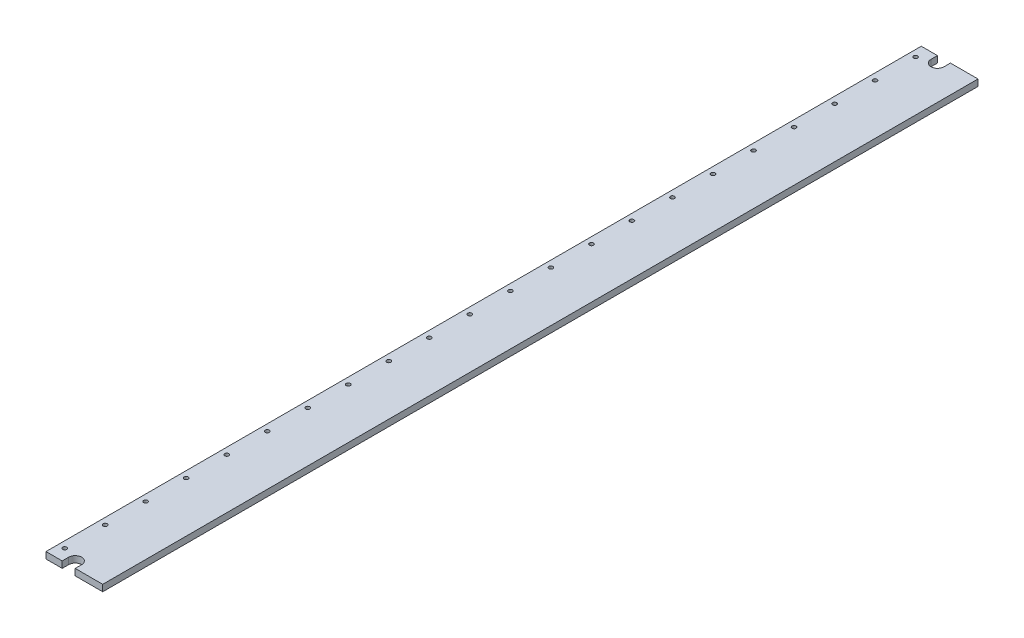
SolidWorks part; units mm, degrees
ref_plane "Front Plane" through (0, 0, 0) normal (0, 0, 1) x (1, 0, 0)
ref_plane "Top Plane" through (0, 0, 0) normal (0, 1, 0) x (1, 0, 0)
ref_plane "Right Plane" through (0, 0, 0) normal (1, 0, 0) x (0, 0, -1)
sketch "Sketch1" plane through (0, 0, 0) normal (0, 0, 1) x (1, 0, 0)
  line L1 (-16.5, -2) -> (18.5, -2)
  line L2 (-16.5, -2) -> (-16.5, 2)
  line L3 (-16.5, 2) -> (18.5, 2)
  line L4 (18.5, -2) -> (18.5, 2)
  line L5 (-16.5, -2) -> (18.5, 2) construction
  line L6 (-16.5, 2) -> (18.5, -2) construction
  point P0 (1, 0)
  dimension "D1" = 4
  dimension "D2" = 35
extrude "Boss-Extrude1" add sketch "Sketch1" along normal blind 540
sketch "Sketch2" plane through (0, 2, 0) normal (0, 1, 0) x (1, 0, 0)
  line L0 (-16.5, -540) -> (-16.5, 0) construction
  line L1 (18.5, 0) -> (-16.5, 0) construction
  point P0 (-12.5, -7.5)
  dimension "D1" = 4
  dimension "D2" = 7.5
hole_wizard "M3 Tapped Hole1" positions "3DSketch1" profile "Sketch3" tap size "M3" standard "DIN" end condition through all
sketch3d "3DSketch1"
  point P0 (-12.5, 2, 7.5)
sketch "Sketch3" plane through (-12.5, 2, 7.5) normal (1, 0, 0) x (0, 0, 1)
  line L0 (0, 0) -> (0, 4)
  line L1 (0, 4) -> (1.25, 4)
  line L2 (1.25, 4) -> (1.25, 0)
  line L5 (1.25, 0) -> (0, 0)
  line L11 (0, -6.35) -> (0, 107.95) construction
  dimension "Thread Major Dia." = 2.5
  dimension "Thru Tap Drill Depth" = 4
pattern_linear "LPattern1" count 22 spacing 25 along (0, 0, 1) of "M3 Tapped Hole1"
sketch "Sketch4" plane through (0, 2, 0) normal (0, 1, 0) x (1, 0, 0)
  line L0 (-6.5, 0) -> (-6.5, -4)
  line L1 (18.5, 0) -> (-16.5, 0) construction
  line L2 (1.5, 0) -> (1.5, -4)
  line L3 (-16.5, -540) -> (-16.5, 0) construction
  line L4 (1.5, 0) -> (-6.5, 0)
  line L5 (-6.5, -540) -> (-6.5, -536)
  line L6 (18.5, -540) -> (-16.5, -540) construction
  line L7 (1.5, -540) -> (1.5, -536)
  line L8 (-6.5, -540) -> (1.5, -540)
  arc A0 (-6.5, -4) -> (1.5, -4) centre (-2.5, -4) ccw
  arc A1 (-6.5, -536) -> (1.5, -536) centre (-2.5, -536) cw
  dimension "D1" = 8
  dimension "D2" = 4
  dimension "D3" = 14
  dimension "D4" = 4
extrude "Cut-Extrude1" cut sketch "Sketch4" against normal up to next
